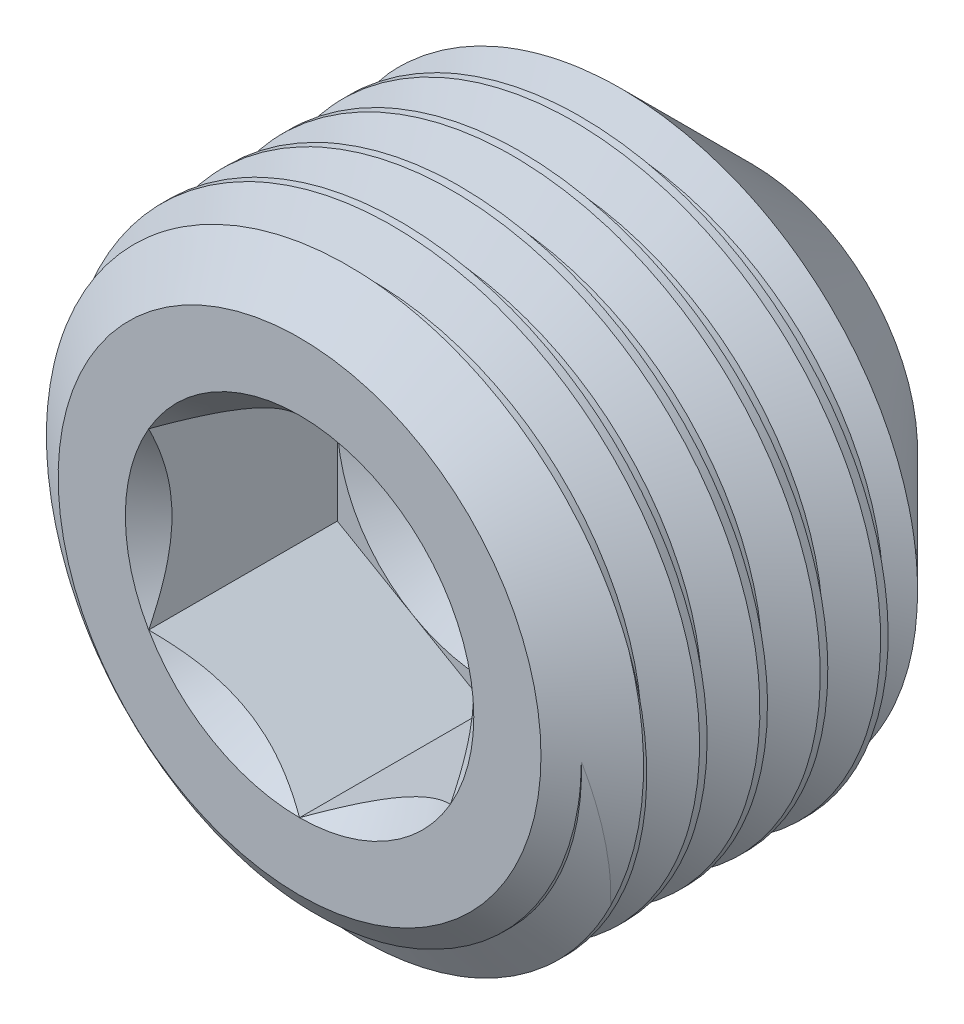
SolidWorks part; units mm, degrees
ref_plane "Front" through (0, 0, 0) normal (0, 0, 1) x (1, 0, 0)
ref_plane "Top" through (0, 0, 0) normal (0, 1, 0) x (1, 0, 0)
ref_plane "Right" through (0, 0, 0) normal (1, 0, 0) x (0, 0, -1)
sketch "Sketch22" plane through (0, 0, 0) normal (1, 0, 0) x (0, 0, -1)
  line L0 (-3.7171, 0) -> (-3.7171, 5.08)
  line L1 (-3.7171, 5.08) -> (-2.8279, 6.35)
  line L2 (-2.8279, 6.35) -> (2.9374, 6.35)
  line L3 (2.9374, 6.35) -> (5.8079, 3.4796)
  line L4 (5.8079, 3.4796) -> (3.7171, 0)
  line L5 (3.7171, 0) -> (-3.7171, 0)
  line L6 (3.7171, 0) -> (5.8079, 0) construction
  line L7 (5.8079, 0) -> (5.8079, 3.4796) construction
  line L8 (5.8079, -3.4796) -> (3.7171, 0) construction
  line L9 (-2.8279, -6.35) -> (2.9374, -6.35) construction
  dimension "Dia" = 12.7
  dimension "Length" = 9.525
  dimension "D3" = 35
  dimension "D5" = 118
  dimension "D6" = 45
  dimension "D7" = 10.16
revolve "Revolve1" add sketch "Sketch22" angle 360 about L6
ref_plane "Plane1" through (0, 0, -5.8079) normal (0, 0, 1) x (1, 0, 0)
sketch "Sketch27" plane through (0, 0, -5.8079) normal (0, 0, 1) x (1, 0, 0)
  circle A0 centre (0, 0) radius 6.35 construction
  circle A1 centre (0, 0) radius 6.35
curve "Helix/Spiral1" pitch 1.27 height 11.1862 radius 6.35 centre (0, 0, -5.8079) axis (0, 0, 1) start towards (1, 0, 0)
sketch "Sketch28" plane through (0, 0, 0) normal (1, 0, 0) x (0, 0, -1)
  line L0 (5.8079, 6.35) -> (6.9191, 6.35)
  line L1 (6.9191, 6.35) -> (6.4746, 5.5801)
  line L2 (6.4746, 5.5801) -> (6.2524, 5.5801)
  line L3 (6.2524, 5.5801) -> (5.8079, 6.35)
  line L4 (6.0301, 5.9651) -> (6.6969, 5.9651) construction
  line L6 (-2.8279, 6.35) -> (2.9374, 6.35) construction
  line L7 (5.8079, 6.985) -> (5.8079, -6.985) construction
  dimension "D1" = 0.2222
  dimension "D3" = 60
  dimension "D2" = 1.1113
sweep "Cut-Sweep2" cut profiles "Sketch28" path "Helix/Spiral1" align with end faces yes
sketch "Sketch23" plane through (0, 0, 3.7171) normal (0, 0, 1) x (1, 0, 0)
  line L1 (0, 3.6662) -> (-3.175, 1.8331)
  line L2 (-3.175, 1.8331) -> (-3.175, -1.8331)
  line L3 (-3.175, -1.8331) -> (0, -3.6662)
  line L4 (0, -3.6662) -> (3.175, -1.8331)
  line L5 (3.175, -1.8331) -> (3.175, 1.8331)
  line L6 (3.175, 1.8331) -> (0, 3.6662)
  circle A0 centre (0, 0) radius 3.175 construction
  dimension "Hex" = 6.35
extrude "Cut-Extrude10" cut sketch "Sketch23" against normal blind 3.9688
sketch "Sketch24" plane through (0, 0, 3.7171) normal (0, 0, 1) x (1, 0, 0)
  circle A0 centre (0, 0) radius 3.6662
extrude "Cut-Extrude11" cut sketch "Sketch24" against normal through all draft 45
sketch "Sketch26" plane through (0, 0, -0.2516) normal (0, 0, 1) x (1, 0, 0)
  circle A0 centre (0, 0) radius 3.175 construction
  circle A1 centre (0, 0) radius 3.175
extrude "Cut-Extrude12" cut sketch "Sketch26" against normal through all draft 60
sketch "Sketch30" plane through (0, 0, 0) normal (1, 0, 0) x (0, 0, -1)
  line L0 (-2.8279, 6.35) -> (2.9374, 6.35) construction
  line L1 (-3.7171, 0) -> (-3.7171, 5.08) construction
  line L2 (5.8079, 0) -> (5.8079, 3.4796) construction
  line L3 (-2.8279, -6.35) -> (2.9374, -6.35) construction
  point P0 (-3.7171, 6.35)
  point P1 (5.8079, 6.35)
  point P2 (5.8079, -6.35)
  point P11 (2.6329, -6.35)
  dimension "D1" = 3.175
sketch "Sketch31" plane through (0, 0, 0) normal (1, 0, 0) x (0, 0, -1)
  line L2 (3.7171, 0) -> (5.8079, -3.4796)
  line L3 (5.8079, 3.4796) -> (3.7171, 0)
equation "\"D7@Sketch22\"=\"Dia@Sketch22\"*.8"
equation "\"D1@Sketch28\" = \"D4@Helix/Spiral1\" * .175"
equation "\"D3@Helix/Spiral1\" = \"Length@Sketch22\" + .0654"
equation "\"D1@Sketch30\" = \"D4@Helix/Spiral1\" * 2.5"
equation "\"hex Depth@Cut-Extrude10\" = \"Hex@Sketch23\" * .625"
equation "\"D2@Sketch28\" = \"D4@Helix/Spiral1\" * .875"
